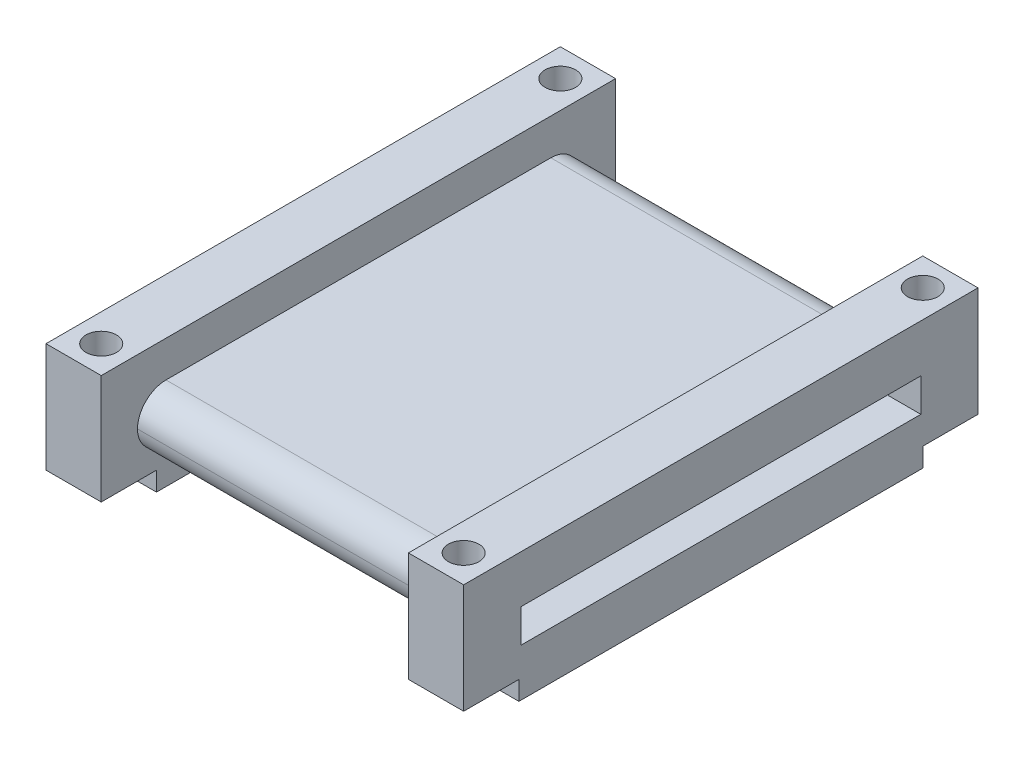
SolidWorks part; units mm, degrees
ref_plane "Front Plane" through (0, 0, 0) normal (0, 0, 1) x (1, 0, 0)
ref_plane "Top Plane" through (0, 0, 0) normal (0, 1, 0) x (1, 0, 0)
ref_plane "Right Plane" through (0, 0, 0) normal (1, 0, 0) x (0, 0, -1)
sketch "Sketch1" plane through (0, 0, 0) normal (1, 0, 0) x (0, 0, -1)
  line L0 (23.2, 5.9) -> (23.2, 0) construction
  line L1 (0, 0) -> (46.4, 0)
  line L2 (0, 0) -> (0, 5.9)
  line L3 (0, 5.9) -> (46.4, 5.9)
  line L4 (46.4, 0) -> (46.4, 5.9)
  line L6 (2.2, 1.2) -> (44.2, 1.2)
  line L7 (2.2, 1.2) -> (2.2, 4.7)
  line L8 (2.2, 4.7) -> (44.2, 4.7)
  line L9 (44.2, 1.2) -> (44.2, 4.7)
  line L10 (2.2, 1.2) -> (44.2, 4.7) construction
  line L11 (2.2, 4.7) -> (44.2, 1.2) construction
  point P7 (23.2, 2.95)
  dimension "D1" = 46.4
  dimension "D2" = 5.9
  dimension "D3" = 3.5
  dimension "D4" = 42
extrude "Boss-Extrude1" add sketch "Sketch1" along normal blind 32.25
fillet "Fillet2" radius 3 4 edges at (16.125, 0, -46.4) (16.125, 0, 0) (16.125, 5.9, 0) (16.125, 5.9, -46.4)
sketch "Sketch2" plane through (32.25, 0, 0) normal (1, 0, 0) x (0, 0, -1)
  line L0 (23.2, 5.9) -> (23.2, 0) construction
  line L1 (43.4, 5.9) -> (3, 5.9) construction
  line L2 (3, 0) -> (43.4, 0) construction
  line L4 (-3.8, -3.8) -> (50.2, -3.8)
  line L5 (-3.8, -3.8) -> (-3.8, 9.7)
  line L6 (-3.8, 9.7) -> (50.2, 9.7)
  line L7 (50.2, -3.8) -> (50.2, 9.7)
  line L8 (-3.8, -3.8) -> (50.2, 9.7) construction
  line L9 (-3.8, 9.7) -> (50.2, -3.8) construction
  line L14 (44.2, 1.2) -> (2.2, 1.2)
  line L15 (44.2, 1.2) -> (44.2, 4.7)
  line L16 (44.2, 4.7) -> (2.2, 4.7)
  line L17 (2.2, 1.2) -> (2.2, 4.7)
  line L18 (44.2, 1.2) -> (2.2, 4.7) construction
  line L19 (44.2, 4.7) -> (2.2, 1.2) construction
  point P6 (23.2, 2.95)
  point P11 (23.2, 2.95)
  point P12 (23.2, 2.95)
  dimension "D1" = 13.5
  dimension "D2" = 54
extrude "Boss-Extrude2" add sketch "Sketch2" along normal blind 5.8
sketch "Sketch3" plane through (0, 0, 0) normal (-1, 0, 0) x (0, 0, 1)
  line L0 (-23.2, 5.9) -> (-23.2, 0) construction
  line L1 (-43.4, 5.9) -> (-3, 5.9) construction
  line L2 (-3, 0) -> (-43.4, 0) construction
  line L4 (3.8, -3.8) -> (-50.2, -3.8)
  line L5 (3.8, -3.8) -> (3.8, 9.7)
  line L6 (3.8, 9.7) -> (-50.2, 9.7)
  line L7 (-50.2, -3.8) -> (-50.2, 9.7)
  line L8 (3.8, -3.8) -> (-50.2, 9.7) construction
  line L9 (3.8, 9.7) -> (-50.2, -3.8) construction
  line L10 (-2.2, 1.2) -> (-44.2, 1.2)
  line L11 (-2.2, 1.2) -> (-2.2, 4.7)
  line L12 (-2.2, 4.7) -> (-44.2, 4.7)
  line L13 (-44.2, 1.2) -> (-44.2, 4.7)
  line L14 (-2.2, 1.2) -> (-44.2, 4.7) construction
  line L15 (-2.2, 4.7) -> (-44.2, 1.2) construction
  point P6 (-23.2, 2.95)
  point P12 (-23.2, 2.95)
extrude "Boss-Extrude3" add sketch "Sketch3" along normal blind 5.8
sketch "Sketch4" plane through (0, 9.7, 0) normal (0, 1, 0) x (1, 0, 0)
  line L0 (-2.9, 50.2) -> (-2.9, 47.3) construction
  line L1 (-5.8, 50.2) -> (0, 50.2) construction
  line L2 (35.15, 50.2) -> (35.15, 47.3) construction
  line L3 (38.05, 50.2) -> (32.25, 50.2) construction
  line L4 (-2.9, -3.8) -> (-2.9, -0.9) construction
  line L5 (-5.8, -3.8) -> (0, -3.8) construction
  line L6 (35.15, -3.8) -> (35.15, -0.9) construction
  line L7 (38.05, -3.8) -> (32.25, -3.8) construction
  circle A0 centre (-2.9, 47.3) radius 1.6
  circle A1 centre (35.15, 47.3) radius 1.6
  circle A2 centre (-2.9, -0.9) radius 1.6
  circle A3 centre (35.15, -0.9) radius 1.6
  dimension "D2" = 3.2
  dimension "D4" = 3.2
  dimension "D6" = 3.2
  dimension "D8" = 3.2
  dimension "D1" = 2.9
  dimension "D3" = 2.9
  dimension "D5" = 2.9
  dimension "D7" = 2.9
extrude "Cut-Extrude1" cut sketch "Sketch4" against normal through all
sketch "Sketch6" plane through (38.05, 0, 0) normal (1, 0, 0) x (0, 0, -1)
  line L0 (50.2, -3.8) -> (50.2, 9.7) construction
  line L1 (-3.8, -3.8) -> (50.2, -3.8)
  line L2 (-3.8, -3.8) -> (-3.8, 3.4)
  line L3 (-3.8, 3.4) -> (50.2, 3.4)
  line L4 (50.2, -3.8) -> (50.2, 3.4)
  dimension "D1" = 7.2
extrude "Cut-Extrude2" [suppressed] cut sketch "Sketch6" against normal blind 5.8
sketch "Sketch7" plane through (-5.8, 0, 0) normal (-1, 0, 0) x (0, 0, 1)
  line L0 (3.8, -3.8) -> (3.8, 9.7) construction
  line L1 (-50.2, -3.8) -> (3.8, -3.8)
  line L2 (-50.2, -3.8) -> (-50.2, 3.4)
  line L3 (-50.2, 3.4) -> (3.8, 3.4)
  line L4 (3.8, -3.8) -> (3.8, 3.4)
  dimension "D1" = 7.2
extrude "Cut-Extrude3" [suppressed] cut sketch "Sketch7" against normal blind 5.8
sketch "Sketch15" plane through (-5.8, 0, 0) normal (-1, 0, 0) x (0, 0, 1)
  line L1 (-44.2, 1.2) -> (-2.2, 1.2)
  line L2 (-44.2, 1.2) -> (-44.2, 4.7)
  line L3 (-44.2, 4.7) -> (-2.2, 4.7)
  line L4 (-2.2, 1.2) -> (-2.2, 4.7)
  line L5 (-50.2, -3.8) -> (-44.4, -3.8)
  line L6 (-50.2, -3.8) -> (-50.2, -1.8)
  line L7 (-50.2, -1.8) -> (-44.4, -1.8)
  line L8 (-44.4, -3.8) -> (-44.4, -1.8)
  line L9 (3.8, -3.8) -> (-2, -3.8)
  line L10 (3.8, -3.8) -> (3.8, -1.8)
  line L11 (3.8, -1.8) -> (-2, -1.8)
  line L12 (-2, -3.8) -> (-2, -1.8)
  dimension "D1" = 5.8
  dimension "D2" = 2
  dimension "D3" = 5.8
  dimension "D4" = 2
extrude "Cut-Extrude5" cut sketch "Sketch15" against normal through all
fillet "Fillet3" radius 2 1 edges at (-5.8, -3.8, -23.2)
